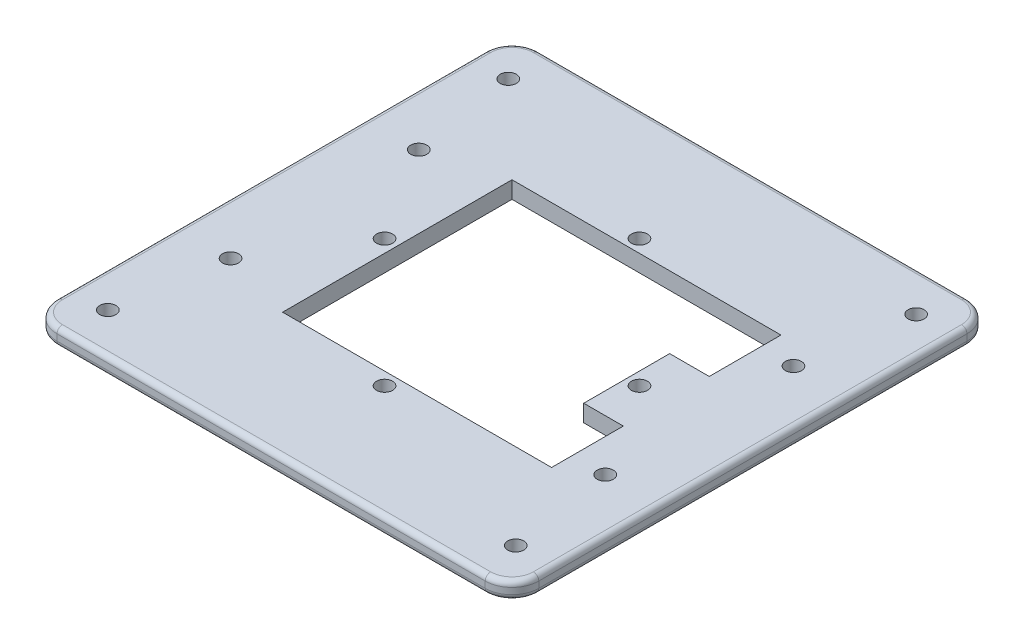
SolidWorks part; units mm, degrees
ref_plane "Front Plane" through (0, 0, 0) normal (0, 0, 1) x (1, 0, 0)
ref_plane "Top Plane" through (0, 0, 0) normal (0, 1, 0) x (1, 0, 0)
ref_plane "Right Plane" through (0, 0, 0) normal (1, 0, 0) x (0, 0, -1)
sketch "Sketch2" plane through (0, 0, 0) normal (0, 1, 0) x (1, 0, 0)
  line L0 (58.412, -27.6709) -> (-21.588, -27.6709)
  line L1 (-26.588, -22.6709) -> (-26.588, 57.329)
  line L2 (-21.588, 62.329) -> (58.412, 62.3283)
  line L3 (63.412, 57.3283) -> (63.412, -22.6709)
  line L4 (39.8395, -4.0986) -> (-3.0155, -4.0986)
  line L6 (-3.0155, 38.7564) -> (39.8395, 38.7564)
  line L7 (39.8395, 38.7564) -> (39.8395, -4.0986)
  line L11 (-3.0155, 38.7564) -> (-3.0155, -4.0986)
  arc A0 (63.412, 57.3283) -> (58.412, 62.3283) centre (58.412, 57.3283) ccw
  arc A1 (58.412, -27.6709) -> (63.412, -22.6709) centre (58.412, -22.6709) ccw
  arc A2 (-21.588, -27.6709) -> (-26.588, -22.6709) centre (-21.588, -22.6709) cw
  arc A3 (-21.588, 62.329) -> (-26.588, 57.329) centre (-21.588, 57.329) ccw
  point P0 (18.412, -4.0986)
  point P1 (-21.2336, 35.0739)
  point P2 (-3.0155, 17.3289)
  point P7 (63.412, 62.3282)
  point P20 (-26.588, -27.6709)
  point P23 (-26.588, 62.3291)
  dimension "D3" = 5
  dimension "D2" = 42.855
  dimension "D4" = 45
  dimension "D5" = 42.855
  dimension "D6" = 42.855
  dimension "D7" = 45
  dimension "D9" = 42.855
  dimension "D18" = 90
  dimension "D19" = 90
extrude "Aluminum plate" add sketch "Sketch2" along normal blind 3.175
ref_axis "Axis4" through (18.412, 3.175, 4.0986) along (0, 0, -1)
ref_axis "Axis2" through (39.8395, 3.175, -17.3289) along (-1, 0, 0)
ref_plane "Plane8" through (0, 0, -17.3289) normal (0, 0, 1) x (1, 0, 0)
ref_plane "Plane10" through (18.412, 0, 0) normal (1, 0, 0) x (0, 0, -1)
ref_axis "Axis8" through (18.412, 48.1723, -17.3289) along (0, -1, 0)
sketch "Sketch5" plane through (0, 3.175, 0) normal (0, 1, 0) x (1, 0, 0)
  line L0 (39.8395, 9.3017) -> (39.8395, -4.0986)
  line L1 (39.8395, 38.7564) -> (47.2341, 38.7564)
  line L2 (39.8395, 38.7564) -> (39.8395, 25.356)
  line L3 (39.8395, 25.356) -> (47.2341, 25.356)
  line L4 (47.2341, 38.7564) -> (47.2341, 25.356)
  line L5 (39.8395, 9.3017) -> (47.2341, 9.3017)
  line L6 (47.2341, 9.3017) -> (47.2341, -4.0986)
  line L7 (39.8395, -4.0986) -> (47.2341, -4.0986)
  dimension "D2" = 16.0542
  dimension "D3" = 13.4004
  dimension "D1" = 2
extrude "Cut-Extrude18" cut sketch "Sketch5" against normal blind 3.175
hole_wizard "Ø3.0 (3) Diameter Hole3" positions "Sketch13" profile "Sketch12" hole size "Ø3.0" standard "Ansi Metric"
sketch "Sketch13" plane through (0, 3.175, 0) normal (0, 1, 0) x (-1, 0, 0)
  line L0 (26.588, -57.329) -> (26.588, 22.6709) construction
  point P1 (16.588, -34.9096)
  dimension "D1" = 10
sketch "Sketch12" plane through (-16.588, 3.175, -34.9096) normal (1, 0, 0) x (0, 0, 1)
  line L0 (0, 0) -> (0, 26.3013)
  line L1 (0, 26.3013) -> (1.5, 25.4)
  line L2 (1.5, 25.4) -> (1.5, 0)
  line L5 (1.5, 0) -> (0, 0)
  line L10 (0, 26.3013) -> (-1.5, 25.4) construction
  line L11 (0, -6.35) -> (0, 107.95) construction
  dimension "Hole Dia." = 3
  dimension "Hole Depth" = 25.4
  dimension "Drill Angle" = 118
pattern_linear "LPattern1" count 2 spacing 70 along (1, 0, 0) count 2 spacing 35.1615 along (0, 0, 1) of "Ø3.0 (3) Diameter Hole3"
hole_wizard "Ø3.0 (3) Diameter Hole4" positions "Sketch15" profile "Sketch14" hole size "Ø3.0" standard "Ansi Metric"
sketch "Sketch15" plane through (0, 3.175, 0) normal (0, 1, 0) x (-1, 0, 0)
  line L0 (-18.412, 4.0986) -> (-18.412, -38.7564) construction
  point P0 (-42.222, -17.3292)
  dimension "D1" = 23.81
sketch "Sketch14" plane through (42.222, 3.175, -17.3292) normal (1, 0, 0) x (0, 0, 1)
  line L0 (0, 0) -> (0, 26.3013)
  line L1 (0, 26.3013) -> (1.5, 25.4)
  line L2 (1.5, 25.4) -> (1.5, 0)
  line L5 (1.5, 0) -> (0, 0)
  line L10 (0, 26.3013) -> (-1.5, 25.4) construction
  line L11 (0, -6.35) -> (0, 107.95) construction
  dimension "Hole Dia." = 3
  dimension "Hole Depth" = 25.4
  dimension "Drill Angle" = 118
pattern_circular "CirPattern1" count 4 every 90 about axis through (18.412, 48.1723, -17.3289) along (0, -1, 0) of "Ø3.0 (3) Diameter Hole4"
hole_wizard "Ø3.0 (3) Diameter Hole5" positions "Sketch17" profile "Sketch16" hole size "Ø3.0" standard "Ansi Metric"
sketch "Sketch17" plane through (0, 0, 0) normal (0, -1, 0) x (1, 0, 0)
  line L0 (-26.588, -57.329) -> (-26.588, 22.6709) construction
  line L1 (-21.588, 27.6709) -> (58.412, 27.6709) construction
  point P5 (-19.688, -54.7306)
  point P14 (56.512, -54.7306)
  point P16 (56.512, 20.0724)
  point P18 (-19.688, 20.0724)
  dimension "D1" = 74.803
  dimension "D2" = 74.803
  dimension "D3" = 76.2
  dimension "D4" = 76.2
  dimension "D5" = 6.9
  dimension "D6" = 7.5985
  dimension "D7" = 6.9
  dimension "D8" = 7.5985
sketch "Sketch16" plane through (-19.688, 0, -54.7306) normal (1, 0, 0) x (0, 0, -1)
  line L0 (0, 0) -> (0, 26.3013)
  line L1 (0, 26.3013) -> (1.5, 25.4)
  line L2 (1.5, 25.4) -> (1.5, 0)
  line L5 (1.5, 0) -> (0, 0)
  line L10 (0, 26.3013) -> (-1.5, 25.4) construction
  line L11 (0, -6.35) -> (0, 107.95) construction
  dimension "Hole Dia." = 3
  dimension "Hole Depth" = 25.4
  dimension "Drill Angle" = 118
fillet "Fillet1" radius 1 16 edges at (-25.1236, 0, 26.2065) (-26.588, 0, -17.3291) (-25.1236, 0, -60.8646) (18.412, 0, -62.3286) (61.9475, 0, -60.8638) (63.412, 0, -17.3287) (61.9475, 0, 26.2065) (61.9475, 3.175, -60.8638) (63.412, 3.175, -17.3287) (61.9475, 3.175, 26.2065) (18.412, 3.175, 27.6709) (-25.1236, 3.175, 26.2065) (-26.588, 3.175, -17.3291) (-25.1236, 3.175, -60.8646) (18.412, 0, 27.6709) (18.412, 3.175, -62.3286)
equation "\"D7@Sketch2\" = \"D18@Sketch2\"/2"
equation "\"D2@Sketch5\" = \"D9@Sketch2\"-\"D3@Sketch5\"-\"D3@Sketch5\""
equation "\"D4@Sketch2\" = \"D19@Sketch2\"/2"
equation "\"D2@Sketch17\" = \"D1@Sketch17\""
equation "\"D4@Sketch17\" = \"D3@Sketch17\""
equation "\"D5@Sketch17\" = (\"D19@Sketch2\"-\"D4@Sketch17\")/2"
equation "\"D6@Sketch17\" = (\"D18@Sketch2\"-\"D2@Sketch17\")/2"
equation "\"D7@Sketch17\" = \"D5@Sketch17\""
equation "\"D8@Sketch17\" = \"D6@Sketch17\""
